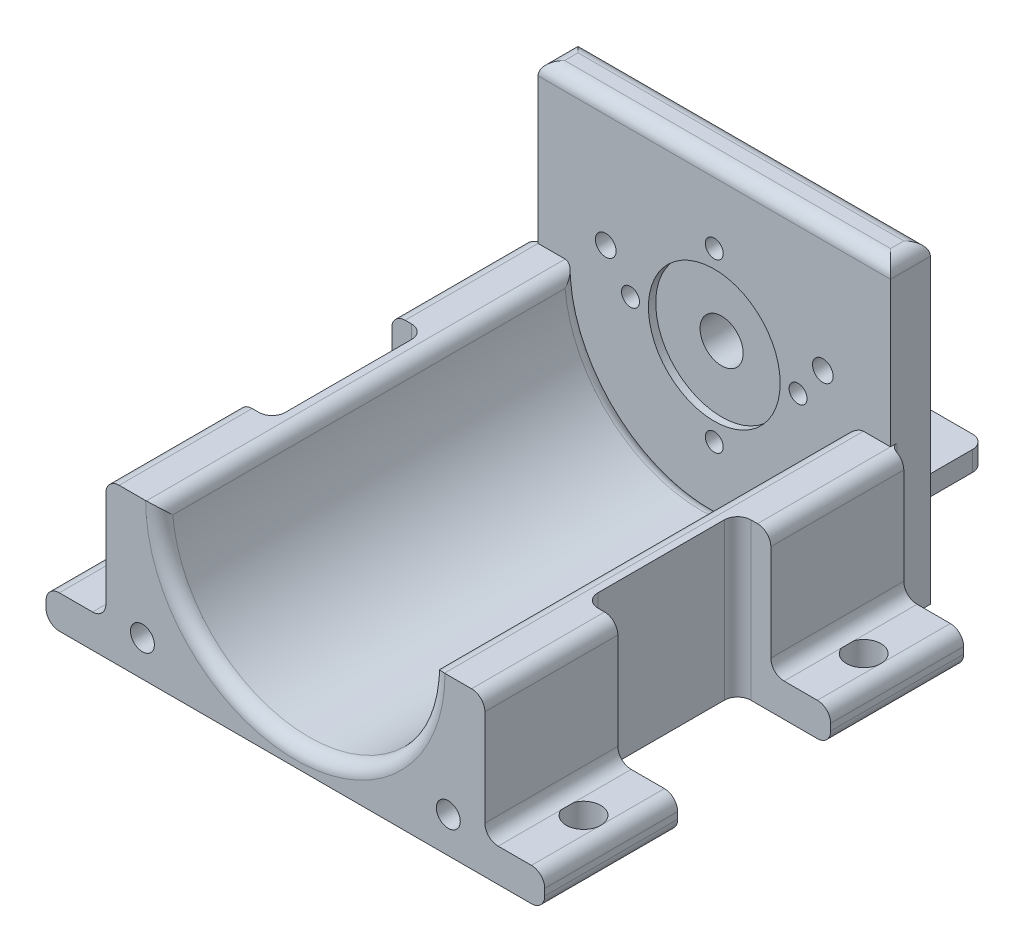
SolidWorks part; units mm, degrees
ref_plane "Front Plane" through (0, 0, 0) normal (0, 0, 1) x (1, 0, 0)
ref_plane "Top Plane" through (0, 0, 0) normal (0, 1, 0) x (1, 0, 0)
ref_plane "Right Plane" through (0, 0, 0) normal (1, 0, 0) x (0, 0, -1)
sketch "Sketch1" plane through (0, 0, 0) normal (0, 0, 1) x (1, 0, 0)
  line L0 (0, 0) -> (-29.845, 0)
  line L1 (-29.845, 0) -> (29.845, 0)
  line L2 (29.845, 0) -> (29.845, -29.845)
  line L3 (29.845, -29.845) -> (0, -29.845)
  line L4 (0, -29.845) -> (-29.845, -29.845)
  line L5 (-29.845, -29.845) -> (-29.845, 0)
  arc A0 (-26.054, 0) -> (26.054, 0) centre (0, 0) ccw
  dimension "D1" = 52.1081
extrude "Boss-Extrude1" add sketch "Sketch1" along normal blind 80.01 contours A0 L1 L5 L4 L3 L2 region at (0, -26.7214, 0)
sketch "Sketch2" plane through (0, 0, 80.01) normal (0, 0, 1) x (1, 0, 0)
  line L0 (-29.845, -23.495) -> (-29.845, 0)
  line L1 (-29.845, -29.845) -> (-45.085, -29.845)
  line L2 (-29.845, -29.845) -> (-29.845, -23.495)
  line L3 (-36.195, -23.495) -> (-45.085, -23.495)
  line L4 (-47.625, -27.305) -> (-47.625, -26.035)
  line L5 (-29.845, 0) -> (-36.195, 0)
  line L6 (-36.195, 0) -> (-36.195, -23.495)
  line L7 (0, 0) -> (0, -60.6078) construction
  line L8 (29.845, -23.495) -> (29.845, 0)
  line L9 (29.845, 0) -> (36.195, 0)
  line L10 (47.625, -27.305) -> (47.625, -26.035)
  line L11 (36.195, -23.495) -> (45.085, -23.495)
  line L12 (29.845, -29.845) -> (29.845, -23.495)
  line L13 (29.845, -29.845) -> (45.085, -29.845)
  line L14 (36.195, 0) -> (36.195, -23.495)
  arc A0 (-45.085, -29.845) -> (-47.625, -27.305) centre (-45.085, -27.305) cw
  arc A1 (-45.085, -23.495) -> (-47.625, -26.035) centre (-45.085, -26.035) ccw
  arc A2 (45.085, -29.845) -> (47.625, -27.305) centre (45.085, -27.305) ccw
  arc A3 (47.625, -26.035) -> (45.085, -23.495) centre (45.085, -26.035) ccw
  point P21 (-47.625, -29.845)
  point P24 (-47.625, -23.495)
  point P28 (47.625, -29.845)
  point P31 (47.625, -23.495)
  dimension "D3" = 2.54
  dimension "D4" = 2.54
  dimension "D1" = 17.78
  dimension "D2" = 6.35
extrude "Boss-Extrude2" add sketch "Sketch2" against normal blind 25.4
sketch "Sketch3" plane through (0, 0, 0) normal (0, 0, -1) x (-1, 0, 0)
  line L0 (-29.845, 0) -> (-36.195, 0)
  line L1 (-36.195, 0) -> (-36.195, -23.495)
  line L2 (-36.195, -23.495) -> (-45.085, -23.495)
  line L3 (-47.625, -26.035) -> (-47.625, -27.305)
  line L4 (36.195, -23.495) -> (45.085, -23.495)
  line L5 (-45.085, -29.845) -> (-29.845, -29.845)
  line L6 (-29.845, -29.845) -> (-29.845, 0)
  line L7 (0, 0) -> (0, -41.5928) construction
  line L8 (47.625, -26.035) -> (47.625, -27.305)
  line L9 (45.085, -29.845) -> (29.845, -29.845)
  line L10 (29.845, 0) -> (36.195, 0)
  line L11 (29.845, -29.845) -> (29.845, 0)
  line L12 (36.195, 0) -> (36.195, -23.495)
  arc A0 (-47.625, -27.305) -> (-45.085, -29.845) centre (-45.085, -27.305) ccw
  arc A1 (-47.625, -26.035) -> (-45.085, -23.495) centre (-45.085, -26.035) cw
  arc A2 (47.625, -26.035) -> (45.085, -23.495) centre (45.085, -26.035) ccw
  arc A3 (47.625, -27.305) -> (45.085, -29.845) centre (45.085, -27.305) cw
  dimension "D1" = 2.54
extrude "Boss-Extrude3" add sketch "Sketch3" against normal blind 25.4
fillet "Fillet1" radius 2.54 4 edges at (26.054, 0, 40.005) (0, -26.054, 80.01) (-26.054, 0, 40.005) (0, -26.054, 0)
fillet "Fillet2" radius 2.54 4 edges at (-36.195, 0, 12.7) (-36.195, 0, 67.31) (36.195, 0, 67.31) (36.195, 0, 12.7)
fillet "Fillet3" radius 2.54 4 edges at (29.845, -14.9225, 25.4) (29.845, -14.9225, 54.61) (-29.845, -14.9225, 54.61) (-29.845, -14.9225, 25.4)
fillet "Fillet4" radius 2.54 4 edges at (36.195, -23.495, 12.7) (36.195, -23.495, 67.31) (-36.195, -23.495, 67.31) (-36.195, -23.495, 12.7)
sketch "Sketch4" plane through (0, -23.495, 0) normal (0, 1, 0) x (1, 0, 0)
  line L1 (38.735, 0) -> (38.735, -25.4) construction
  line L3 (0, 0) -> (0, -97.0513) construction
  line L4 (0, -40.005) -> (67.9571, -40.005) construction
  line L5 (67.9571, -40.005) -> (-53.183, -40.005) construction
  line L6 (-45.085, -25.4) -> (-38.735, -25.4) construction
  circle A0 centre (41.783, -13.2522) radius 3.302
  circle A1 centre (-41.783, -13.2522) radius 3.302
  circle A2 centre (-41.783, -66.7578) radius 3.302
  circle A3 centre (41.783, -66.7578) radius 3.302
  dimension "D1" = 3.048
  dimension "D2" = 6.604
  dimension "D3" = 14.605
extrude "Cut-Extrude1" cut sketch "Sketch4" against normal blind 25.4
sketch "Sketch5" plane through (0, 0, 80.01) normal (0, 0, 1) x (1, 0, 0)
  line L0 (0, 0) -> (0, -55.9591) construction
  circle A0 centre (-29.21, -23.0229) radius 2.286
  arc A1 (-28.594, 0) -> (28.594, 0) centre (0, 0) ccw construction
  circle A2 centre (29.21, -23.0229) radius 2.286
  dimension "D1" = 4.572
  dimension "D2" = 29.21
extrude "Cut-Extrude2" cut sketch "Sketch5" against normal blind 19.05
sketch "Sketch6" plane through (0, 0, 0) normal (0, 0, -1) x (-1, 0, 0)
  line L0 (0, 0) -> (69.6711, 0) construction
  line L1 (-33.655, 0) -> (-33.655, -29.845)
  line L2 (69.6711, 0) -> (-17.7145, 0) construction
  line L3 (-45.085, -29.845) -> (45.085, -29.845) construction
  line L4 (-33.655, 0) -> (-33.655, 18.1047)
  line L5 (33.655, 0) -> (33.655, -29.845)
  line L6 (0, 0) -> (0, 53.7563) construction
  line L7 (33.655, -29.845) -> (-33.655, -29.845)
  line L8 (-26.054, 0) -> (-54.2672, 0) construction
  line L9 (33.655, 18.1047) -> (33.655, 0)
  line L10 (0, 53.7563) -> (0, -48.6927) construction
  line L11 (-33.655, 18.1047) -> (-33.655, 30.2589)
  line L12 (-33.655, 30.2589) -> (33.655, 30.2589)
  line L13 (33.655, 30.2589) -> (33.655, 18.1047)
  circle A1 centre (0, 0) radius 16 construction
  circle A2 centre (0, 16) radius 1.7145
  circle A3 centre (16, 0) radius 1.7145
  circle A4 centre (-16, 0) radius 1.7145
  circle A5 centre (0, -16) radius 1.7145
  dimension "D1" = 32
  dimension "D2" = 3.429
  dimension "D3" = 3.429
  dimension "D4" = 3.429
  dimension "D5" = 3.429
extrude "Boss-Extrude4" add sketch "Sketch6" along normal blind 7.62
fillet "Fillet6" radius 2.54 4 edges at (-33.655, 30.2589, -3.81) (0, 30.2589, -7.62) (33.655, 30.2589, -3.81) (0, 30.2589, 0)
fillet "Fillet8" radius 1.27 2 edges at (-33.655, -14.9225, 0) (33.655, -14.9225, 0)
sketch "Sketch8" plane through (0, -29.845, 0) normal (0, -1, 0) x (1, 0, 0)
  line L0 (-15.875, -7.62) -> (-15.875, -33.4468)
  line L2 (33.655, -7.62) -> (-33.655, -7.62) construction
  line L3 (0, 0) -> (0, -35.9868) construction
  line L4 (15.875, -7.62) -> (15.875, -33.4468)
  line L5 (-47.625, 0) -> (-47.625, -35.9868) construction
  line L6 (-13.335, -35.9868) -> (13.335, -35.9868)
  circle A0 centre (8.255, -22.9695) radius 3.302
  circle A1 centre (-8.255, -22.9695) radius 3.302
  arc A2 (-15.875, -33.4468) -> (-13.335, -35.9868) centre (-13.335, -33.4468) ccw
  arc A3 (15.875, -33.4468) -> (13.335, -35.9868) centre (13.335, -33.4468) cw
  line M17 (-33.655, -7.62) -> (33.655, -7.62)
  dimension "D2" = 6.604
  dimension "D3" = 6.604
  dimension "D4" = 7.62
  dimension "D5" = 7.62
  dimension "D6" = 2.54
  dimension "D1" = 31.75
extrude "Boss-Extrude5" add sketch "Sketch8" against normal blind 3.81 contours A3 L4 L0 A2 L6 A1 A0 M17 region at (0, -29.845, -21.6616)
fillet "Fillet9" radius 3.81 1 edges at (0, -26.035, -7.62)
fillet "Fillet10" radius 1.27 2 edges at (15.875, -26.035, -7.62) (-15.875, -26.035, -7.62)
sketch "Sketch9" plane through (0, 0, -7.62) normal (0, 0, -1) x (-1, 0, 0)
  circle A0 centre (0, 0) radius 4.1148
  dimension "D1" = 8.2296
extrude "Cut-Extrude3" cut sketch "Sketch9" against normal blind 39.116
sketch "Sketch12" plane through (0, 0, 0) normal (0, 0, 1) x (1, 0, 0)
  circle A0 centre (0, 0) radius 12.5857
  dimension "D1" = 25.1714
extrude "Cut-Extrude4" cut sketch "Sketch12" against normal blind 1.4
sketch "Sketch13" plane through (0, 0, -7.62) normal (0, 0, -1) x (-1, 0, 0)
  line L0 (0, -28.594) -> (0, 30.706) construction
  line L1 (0, -28.594) -> (0, 36.2978) construction
  circle A1 centre (20.7282, 6.1699) radius 1.9685
  arc A2 (-28.594, 0) -> (28.594, 0) centre (0, 0) ccw construction
  circle A3 centre (-20.7282, 6.1699) radius 1.9685
  point P0 (0, 0)
  dimension "D2" = 3.937
sketch "Sketch14" plane through (0, 0, 0) normal (0, 0, 1) x (1, 0, 0)
  line L0 (0, -28.594) -> (0, 36.2978) construction
  arc A0 (-28.594, 0) -> (28.594, 0) centre (0, 0) ccw construction
extrude "Cut-Extrude5" cut sketch "Sketch13" against normal through all contours A1
sketch "Sketch16" plane through (0, 0, 0) normal (0, 0, 1) x (1, 0, 0)
  line L0 (0, 36.2978) -> (0, -29.845) construction
  line L1 (45.085, -29.845) -> (-45.085, -29.845) construction
  circle A0 centre (-20.7282, 6.1699) radius 1.9685
  circle A1 centre (20.7282, 6.1699) radius 1.9685
extrude "Cut-Extrude6" cut sketch "Sketch16" against normal through all both and the other way through all
